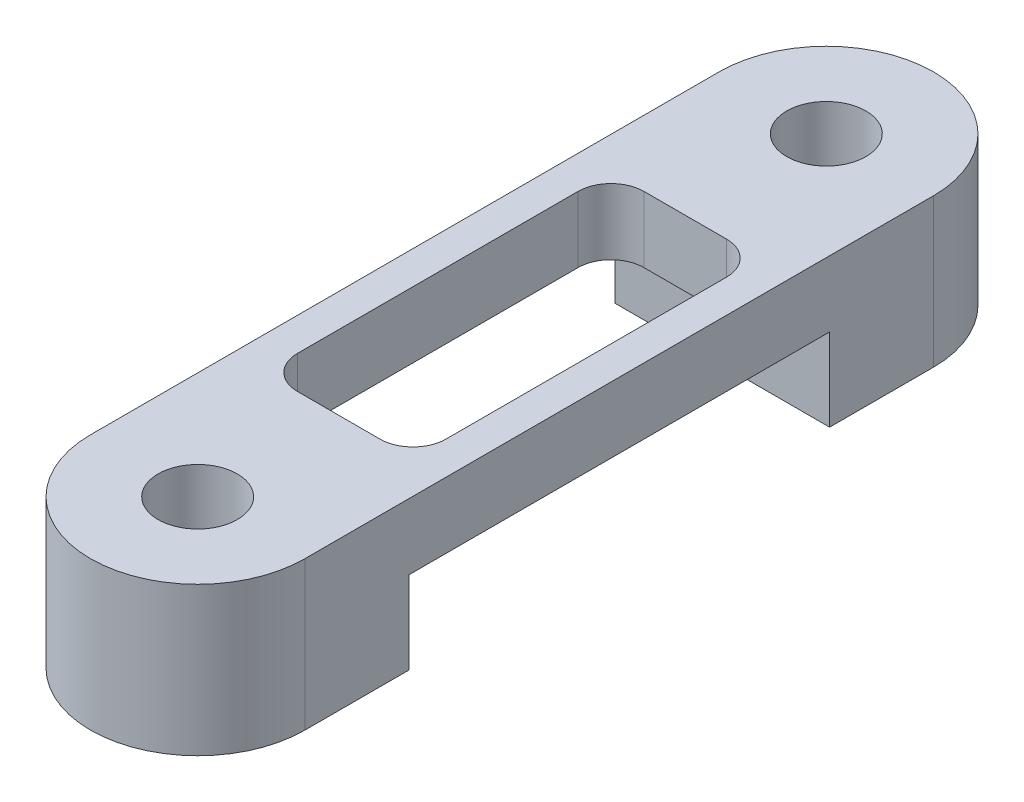
SolidWorks part; units mm, degrees
ref_plane "Front Plane" through (0, 0, 0) normal (0, 0, 1) x (1, 0, 0)
ref_plane "Top Plane" through (0, 0, 0) normal (0, 1, 0) x (1, 0, 0)
ref_plane "Right Plane" through (0, 0, 0) normal (1, 0, 0) x (0, 0, -1)
sketch "Sketch1" plane through (0, 0, 0) normal (0, 1, 0) x (1, 0, 0)
  line L0 (0, 9.525) -> (0, -9.525) construction
  line L1 (6.75, 0) -> (-6.75, 0) construction
  line L2 (6.75, 6.25) -> (-6.75, 6.25)
  line L3 (6.75, 6.25) -> (6.75, -6.25)
  line L4 (6.75, -6.25) -> (-6.75, -6.25)
  line L5 (-6.75, 6.25) -> (-6.75, -6.25)
  line L6 (0, 9.525) -> (0, -9.525) construction
  line L7 (3.25, 9.525) -> (3.25, -9.525)
  line L8 (-3.25, 9.525) -> (-3.25, -9.525)
  line L10 (-3.25, 6.25) -> (-8.75, 6.25)
  line L11 (-3.25, 6.25) -> (-3.25, -6.25)
  line L12 (-3.25, -6.25) -> (-8.75, -6.25)
  line L13 (-8.75, 6.25) -> (-8.75, -6.25)
  line L14 (2.25, 5.25) -> (-2.25, 5.25)
  line L15 (2.25, 5.25) -> (2.25, -5.25)
  line L16 (2.25, -5.25) -> (-2.25, -5.25)
  line L17 (-2.25, 5.25) -> (-2.25, -5.25)
  line L18 (3.25, 6.375) -> (-3.25, 6.375)
  line L19 (3.25, -6.375) -> (-3.25, -6.375)
  circle A0 centre (0, 9.525) radius 1.75
  circle A1 centre (0, -9.525) radius 1.75
  arc A2 (3.25, 9.525) -> (-3.25, 9.525) centre (0, 9.525) ccw
  arc A3 (-3.25, -9.525) -> (3.25, -9.525) centre (0, -9.525) ccw
  point P0 (0, 9.525)
  point P1 (0, -9.525)
  point P4 (0, 0)
  point P14 (0, 0)
  point P23 (2.25, 0)
  dimension "D5" = 3.5
  dimension "D6" = 3.5
  dimension "D7" = 1.5
  dimension "D1" = 19.05
  dimension "D2" = 13.5
  dimension "D3" = 12.5
  dimension "D4" = 6.75
  dimension "D8" = 2
  dimension "D9" = 1
  dimension "D10" = 1
  dimension "D11" = 1
  dimension "D12" = 0.125
  dimension "D13" = 0.125
extrude "Boss-Extrude1" add sketch "Sketch1" against normal blind 2 contours L17 L14 L7 L2 L8 L4 L16 | L8 A3 L7 L19 A1 | A1 | L19 L7 L4 L8 | L7 A2 L8 L18 A0 | A0 | L7 L18 L8 L2 region at (0, 0, -6.3125) region at (0, 0, -6.1091) region at (-3.1588, 0, -7.95) region at (0, 0, 6.3125) region at (0, 0, 6.4662) region at (0, 0, -9.525) region at (0, 0, 9.525)
extrude "Boss-Extrude2" add sketch "Sketch1<3>" against normal blind 2.5 from surface contours L7 A2 L8 L2 A0 | L8 A3 L7 L4 A1 | A0 | A1 region at (-3.1588, 0, -7.95) region at (0, 0, 6.4662) region at (0, 0, -9.525) region at (0, 0, 9.525) starting at face at (0, -2, 0)
sketch "Sketch1<3>" plane through (0, 0, 0) normal (0, 1, 0) x (1, 0, 0) same geometry as "Sketch1"
hole_wizard "M2 Clearance Hole1" positions "Sketch3" profile "Sketch4" hole size "M2" standard "ANSI Metric" end condition through all
sketch "Sketch3" plane through (0, -4.5, 0) normal (0, -1, 0) x (-1, 0, 0)
  point P0 (0, 9.525)
  point P3 (0, -9.525)
sketch "Sketch4" plane through (0, -4.5, -9.525) normal (1, 0, 0) x (0, 0, -1)
  line L0 (0, 0) -> (0, 4.5)
  line L1 (0, 4.5) -> (1.2, 4.5)
  line L2 (1.2, 4.5) -> (1.2, 0)
  line L5 (1.2, 0) -> (0, 0)
  line L11 (0, -6.35) -> (0, 107.95) construction
  dimension "Thru Hole Dia." = 2.4
  dimension "Thru Hole Depth" = 4.5
fillet "Fillet1" radius 1 4 edges at (-2.25, -1, 5.25) (2.25, -1, 5.25) (2.25, -1, -5.25) (-2.25, -1, -5.25)
